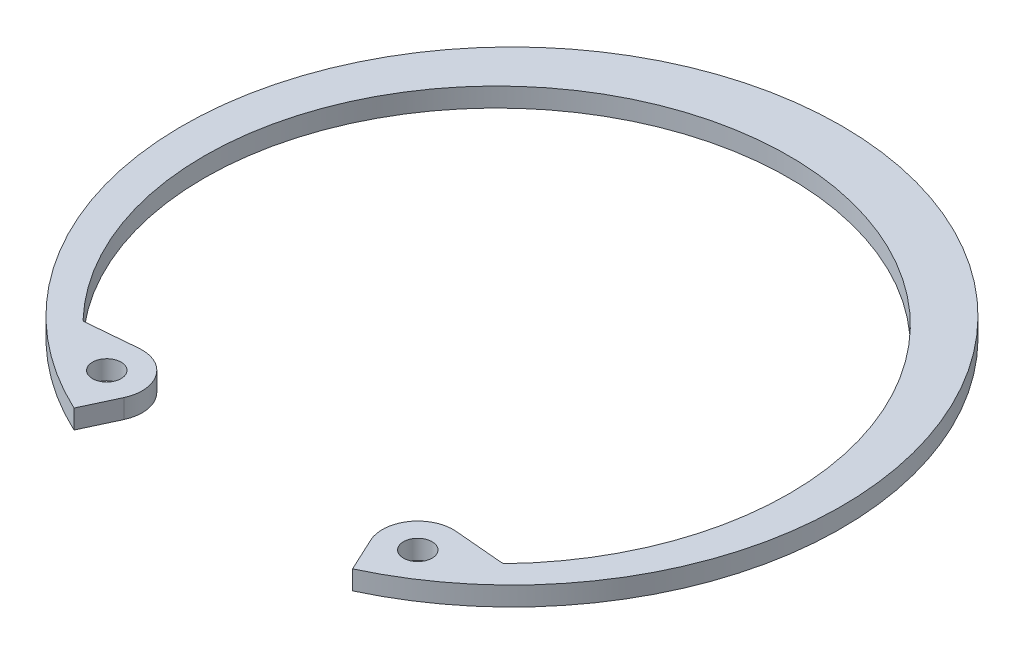
SolidWorks part; units mm, degrees
material "Cast Carbon Steel"
ref_plane "Front" through (0, 0, 0) normal (0, 0, 1) x (1, 0, 0)
ref_plane "Top" through (0, 0, 0) normal (0, 1, 0) x (1, 0, 0)
ref_plane "Right" through (0, 0, 0) normal (1, 0, 0) x (0, 0, -1)
sketch "Sketch2" plane through (0, 0, 0) normal (0, 1, 0) x (1, 0, 0)
  line L0 (0, 0) -> (0, -27.1907) construction
  line L1 (-17.3296, -18.063) -> (-18.8243, -19.6209) construction
  line L2 (11.4913, -24.6431) -> (10.1823, -21.8359)
  line L3 (-11.4913, -24.6431) -> (-10.1823, -21.8359)
  line L4 (0, 22.8727) -> (0, 27.1907) construction
  line L5 (17.3296, -18.063) -> (13.0842, -17.6916)
  line L6 (-17.3296, -18.063) -> (-13.0842, -17.6916)
  line L7 (11.2855, -18.122) -> (-0.395, -25.396) construction
  line L8 (-0.395, -25.396) -> (2.6932, -30.355) construction
  line L9 (2.6932, -30.355) -> (14.3737, -23.081) construction
  line L10 (11.2855, -18.122) -> (14.3737, -23.081) construction
  line L11 (12.8296, -20.6015) -> (10.1823, -21.8359) construction
  line L12 (12.8296, -20.6015) -> (14.3737, -23.081) construction
  line L13 (11.2855, -18.122) -> (-11.2855, -18.122) construction
  line L14 (-11.2855, -18.122) -> (-14.3737, -23.081) construction
  line L15 (-27.1907, 0) -> (27.1907, 0) construction
  arc A1 (11.4913, -24.6431) -> (-11.4913, -24.6431) centre (0, 0) ccw
  arc A2 (17.3296, -18.063) -> (-17.3296, -18.063) centre (0, -1.2633) ccw
  circle A3 centre (0, 0) radius 27.1907 construction
  arc A4 (10.1823, -21.8359) -> (13.0842, -17.6916) centre (12.8296, -20.6015) cw
  arc A5 (-10.1823, -21.8359) -> (-13.0842, -17.6916) centre (-12.8296, -20.6015) ccw
  circle A6 centre (12.8296, -20.6015) radius 1.1811
  circle A7 centre (-12.8296, -20.6015) radius 1.1811
  arc A8 (17.3296, -18.063) -> (-17.3296, -18.063) centre (0, -1.2633) cw construction
  circle A9 centre (0, 0) radius 19.304 construction
  point P5 (12.8296, -20.6015)
  point P10 (11.2855, -18.122)
  dimension "D1" = 60
  dimension "D2" = 60
  dimension "L" = 38.608
  dimension "R" = 2.3622
  dimension "Df" = 54.3814
  dimension "H" = 5.842
  dimension "Angle" = 25
  dimension "Sec. Max" = 4.318
  dimension "Sec. Min" = 2.159
extrude "Extrude1" add sketch "Sketch2" against normal blind 1.5748
fillet "Fillet1" radius 0.254 2 edges at (-17.3296, -0.7874, 18.063) (17.3296, -0.7874, 18.063)
sketch "Sketch3" plane through (0, 0, 0) normal (1, 0, 0) x (0, 0, -1)
  line L0 (-24.6126, -16.4592) -> (-24.6126, -1.651)
  line L1 (-24.6126, -1.651) -> (-26.1112, -1.651)
  line L2 (-26.1112, -1.651) -> (-26.1112, 0.0762)
  line L3 (-26.1112, 0.0762) -> (-24.6126, 0.0762)
  line L4 (-24.6126, 0.0762) -> (-24.6126, 2.4384)
  line L5 (-24.6126, -16.4592) -> (-27.6098, -16.4592)
  line L6 (-24.6126, -1.651) -> (0, -1.651) construction
  line L7 (-24.6126, 2.4384) -> (-27.6098, 2.4384)
  line L8 (0, 130.3401) -> (0, 164.6301) construction
  line L9 (0, -1.651) -> (0, 0.0762) construction
  line L10 (0, 0.0762) -> (-24.6126, 0.0762) construction
  line L11 (-26.1112, -0.7874) -> (0, -0.7874) construction
  line L12 (0, -135.0899) -> (0, 130.3401) construction
  line L13 (-17.9753, -1.5748) -> (22.8727, -1.5748) construction
  line L14 (-27.6098, -16.4592) -> (-27.6098, 2.4384)
  dimension "Shaft Lg" = 18.8976
  dimension "D1" = 0.7874
  dimension "D2" = 1.4986
  dimension "D4" = 1.4986
  dimension "D3" = 2.3622
revolve "Revolve1" [suppressed] add sketch "Sketch3" angle 360 about L8
delete or keep bodies "Body-Delete1" [suppressed] type delete bodies bodies 116
equation "\"D3@Sketch3\" = \"Shaft Lg@Sketch3\"/8"
equation "\"Shaft Lg@Sketch3\" = \"D1@Extrude1\"*12"
equation "\"D1@Sketch3\" = \"D1@Extrude1\"/2"
equation "\"D2@Sketch3\" = \"D4@Sketch3\""
